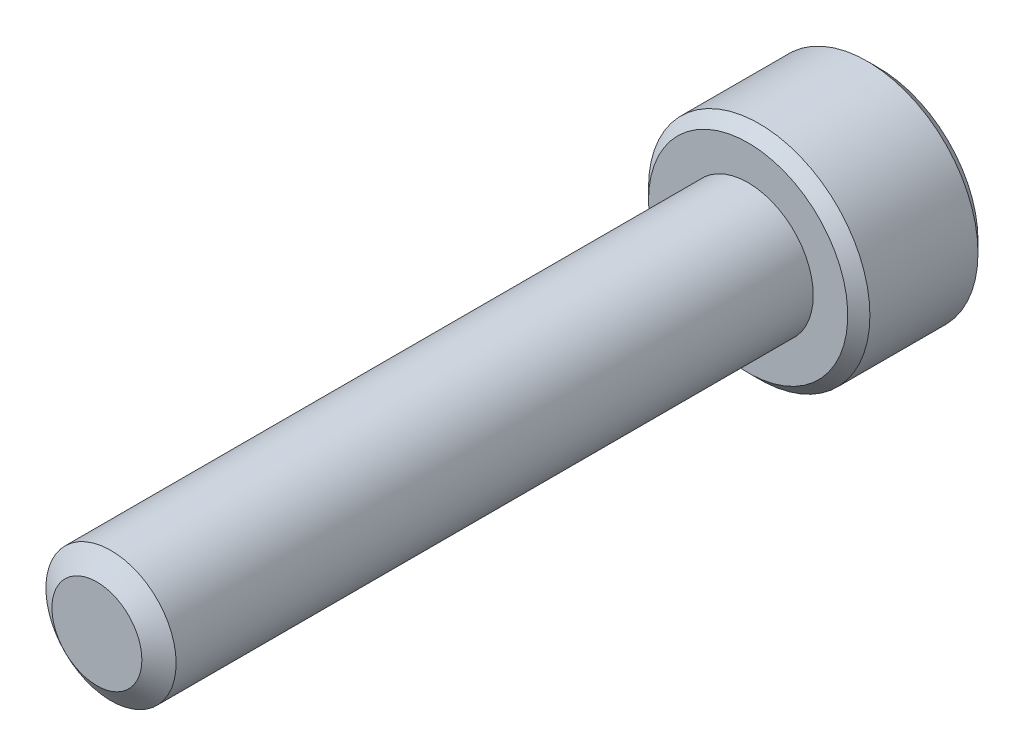
SolidWorks part; units mm, degrees
ref_plane "Front Plane" through (0, 0, 0) normal (0, 0, 1) x (1, 0, 0)
ref_plane "Top Plane" through (0, 0, 0) normal (0, 1, 0) x (1, 0, 0)
ref_plane "Right Plane" through (0, 0, 0) normal (1, 0, 0) x (0, 0, -1)
sketch "Sketch1" plane through (0, 0, 0) normal (0, 0, 1) x (1, 0, 0)
  circle A0 centre (0, 0) radius 2.5
  dimension "OD" = 5
extrude "Extrude1" add sketch "Sketch1" against normal blind 25
sketch "Sketch2" plane through (0, 0, 0) normal (0, 0, 1) x (1, 0, 0)
  circle A0 centre (0, 0) radius 2.5 construction
  circle A1 centre (0, 0) radius 2.5
curve "Helix/Spiral1" pitch 0.8 height 25.8 turns 32.25 parameters "pitch"=0.8
sketch "Sketch3" plane through (0, 0, 0) normal (1, 0, 0) x (0, 0, -1)
  line L0 (-0.7, 2.5) -> (-0.4, 1.9804)
  line L1 (-0.4, 1.9804) -> (-0.3, 1.9804)
  line L2 (-0.3, 1.9804) -> (0, 2.5)
  line L3 (-0.7, 2.5) -> (0, 2.5)
  line L4 (-0.35, 2.5) -> (-0.35, 1.9804) construction
  line L5 (-0.55, 2.2402) -> (-0.15, 2.2402) construction
  line L6 (0, 2.5) -> (0, -2.5) construction
  dimension "D1" = 0.1
  dimension "D2" = 0.4
  dimension "D3" = 60
sweep "Cut-Sweep1" [suppressed] cut profiles "Sketch3" path "Helix/Spiral1"
sketch "Sketch4" plane through (0, 0, 0) normal (1, 0, 0) x (0, 0, -1)
  line L0 (0.5417, 2.5) -> (0, 1.7264)
  line L1 (0, 1.7264) -> (0, 2.5)
  line L2 (0.5417, 2.5) -> (0, 2.5)
  line L3 (-0.7, 2.5) -> (0, 2.5) construction
  line L4 (0, 0) -> (7.0209, 0) construction
  dimension "D1" = 55
  dimension "D2" = 0.254
revolve "Cut-Revolve1" cut sketch "Sketch4" angle 360 about L4
sketch "Sketch5" [suppressed] plane through (0, 0, 0) normal (1, 0, 0) x (0, 0, -1)
  line L0 (25, 0) -> (25, 2.3357) construction
  line L1 (25, 2.627) -> (22.2679, 2.627)
  line L2 (25, 2.627) -> (25, 0)
  line L3 (25, 0) -> (22, 0)
  line L4 (22, 1.627) -> (22, 0)
  line L5 (22.2679, 2.627) -> (22, 1.627)
  line L6 (0, 0) -> (22, 0) construction
  point P3 (22, 2.627)
  point P10 (22, 2.627)
  dimension "D1" = 1
  dimension "D2" = 0.127
  dimension "D3" = 15
  dimension "Thread Min" = 22
revolve "partially thread" [suppressed] add sketch "Sketch5" angle 360 about L6
sketch "Sketch6" plane through (0, 0, -25) normal (0, 0, -1) x (-1, 0, 0)
  circle A0 centre (0, 0) radius 4.25
  dimension "head dia" = 8.5
extrude "Extrude2" add sketch "Sketch6" along normal blind 5
sketch "Sketch7" plane through (0, 0, -30) normal (0, 0, -1) x (-1, 0, 0)
  line L1 (0, 2.3094) -> (-2, 1.1547)
  line L2 (-2, 1.1547) -> (-2, -1.1547)
  line L3 (-2, -1.1547) -> (0, -2.3094)
  line L4 (0, -2.3094) -> (2, -1.1547)
  line L5 (2, -1.1547) -> (2, 1.1547)
  line L6 (2, 1.1547) -> (0, 2.3094)
  circle A0 centre (0, 0) radius 2 construction
  dimension "hex dia" = 4
extrude "Cut-Extrude1" cut sketch "Sketch7" against normal blind 3
sketch "Sketch8" plane through (0, 0, -30) normal (0, 0, -1) x (-1, 0, 0)
  circle A0 centre (0, 0) radius 2.3094
extrude "Cut-Extrude2" cut sketch "Sketch8" against normal through all draft 45
chamfer "Chamfer1" distance 0.425 angle 45 2 edges at (-4.25, 0, -30) (-4.25, 0, -25)
sketch "Sketch9" plane through (0, 0, 0) normal (1, 0, 0) x (0, 0, -1)
  line L0 (0, 2.5) -> (0, -2.5) construction
  line L1 (4.4, 2.5) -> (4.4, -2.5) construction
  dimension "D1" = 4.4
equation "\"D3@Helix/Spiral1\" = \"screw length@Extrude1\"+\"pitch@Helix/Spiral1\""
equation "\"D1@Sketch3\" = \"pitch@Helix/Spiral1\"*.125"
equation "\"D2@Sketch3\" = \"pitch@Helix/Spiral1\"*.5"
equation "\"D1@Cut-Extrude1\" = \"hex dia@Sketch7\"*.75"
equation "\"D1@Chamfer1\" = \"head dia@Sketch6\"*.05"
equation "\"D1@Sketch9\" = \"pitch@Helix/Spiral1\"*5.5"
